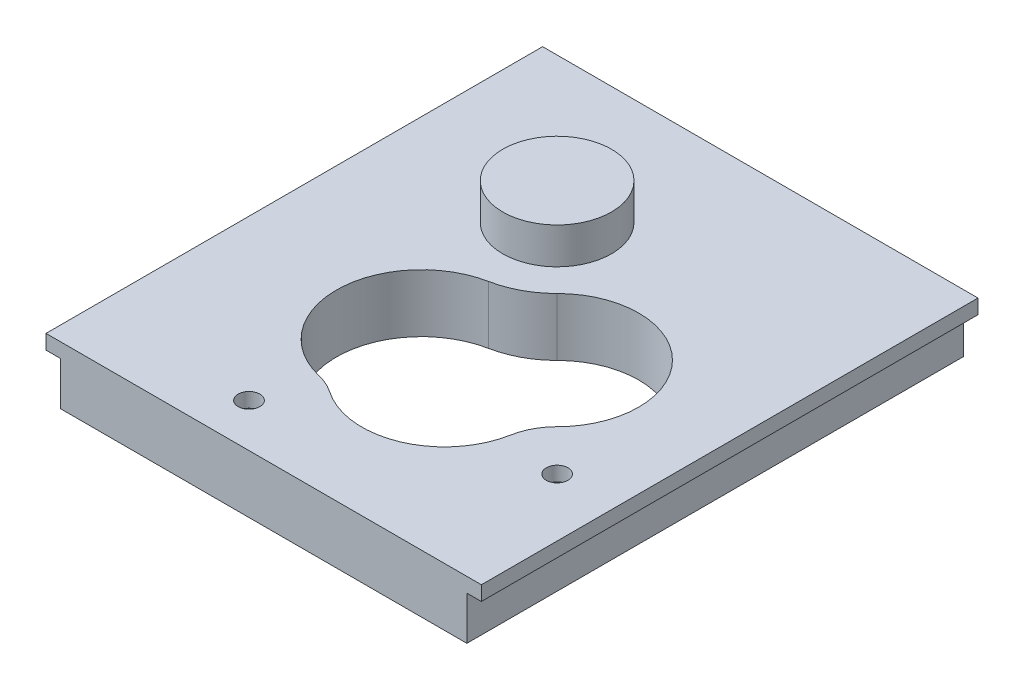
SolidWorks part; units mm, degrees
ref_plane "Front Plane" through (0, 0, 0) normal (0, 0, 1) x (1, 0, 0)
ref_plane "Top Plane" through (0, 0, 0) normal (0, 1, 0) x (1, 0, 0)
ref_plane "Right Plane" through (0, 0, 0) normal (1, 0, 0) x (0, 0, -1)
sketch "Sketch1" plane through (0, 0, 0) normal (0, 1, 0) x (1, 0, 0)
  line L0 (0, 0) -> (30.052, -30.052) construction
  line L1 (0, -42.5) -> (0, 0) construction
  line L3 (-20, 20) -> (36.052, 20)
  line L4 (-20, 20) -> (-20, -48.5)
  line L5 (-20, -48.5) -> (36.052, -48.5)
  line L6 (36.052, 20) -> (36.052, -48.5)
  circle A0 centre (0, 0) radius 7.5
  circle A1 centre (0, -42.5) radius 1.5
  circle A2 centre (30.052, -30.052) radius 1.5
  dimension "D3" = 3
  dimension "D4" = 3
  dimension "D5" = 15
  dimension "D1" = 42.5
  dimension "D2" = 42.5
  dimension "D6" = 45
  dimension "D7" = 6
  dimension "D8" = 6
  dimension "D9" = 20
  dimension "D10" = 20
extrude "Boss-Extrude1" add sketch "Sketch1" against normal blind 8 contours A0 | L6 L3 L4 L5 A2 A1 A0 region at (8.3876, 0, 14.8548) region at (0, 0, 0)
extrude "Boss-Extrude2" add sketch "Sketch1<3>" along normal blind 5 contours A0 region at (0, 0, 0)
sketch "Sketch1<3>" plane through (0, 0, 0) normal (0, 1, 0) x (1, 0, 0) same geometry as "Sketch1"
sketch "Sketch2" plane through (0, -8, 0) normal (0, -1, 0) x (1, 0, 0)
  circle A0 centre (0, 42.5) radius 1.9
  circle A1 centre (30.052, 30.052) radius 1.9
  circle M1 centre (30.052, 30.052) radius 1.5
  circle M2 centre (0, 42.5) radius 1.5
  dimension "D1" = 3.8
extrude "Cut-Extrude1" cut sketch "Sketch2" against normal blind 6 contours A0 M2 | A1 M1 region at (-1.8463, -8, 42.5) region at (28.2058, -8, 30.052)
sketch "Sketch3" plane through (0, 0, 48.5) normal (0, 0, 1) x (1, 0, 0)
  line L1 (-20, 0) -> (-22, 0)
  line L2 (-20, 0) -> (-20, -2)
  line L3 (-20, -2) -> (-22, -2)
  line L4 (-22, 0) -> (-22, -2)
  line L5 (36.052, 0) -> (38.052, 0)
  line L6 (36.052, 0) -> (36.052, -2)
  line L7 (36.052, -2) -> (38.052, -2)
  line L8 (38.052, 0) -> (38.052, -2)
  dimension "D1" = 2
  dimension "D2" = 2
extrude "Boss-Extrude3" add sketch "Sketch3" against normal up to surface (68.5 mm away) up to face at (8.026, -4, -20)
sketch "Sketch4" plane through (0, 0, 0) normal (0, 1, 0) x (1, 0, 0)
  arc A0 (8.4853, -8.4853) -> (2.3202, -11.7736) centre (0, 0) cw
  arc A1 (4.5347, -35.9093) -> (1.8601, -34.7193) centre (0, -42.5) ccw
  arc A2 (2.3202, -11.7736) -> (1.8601, -34.7193) centre (4.591, -23.2966) ccw
  arc A3 (22.1852, -28.5982) -> (24.3952, -24.3952) centre (30.052, -30.052) cw
  arc A4 (8.4853, -8.4853) -> (24.3952, -24.3952) centre (16.4402, -16.4402) cw
  arc A5 (22.1852, -28.5982) -> (4.5347, -35.9093) centre (10.9887, -26.5291) cw
  dimension "D1" = 8
  dimension "D2" = 8
  dimension "D3" = 12
extrude "Cut-Extrude2" cut sketch "Sketch4" against normal blind 10
